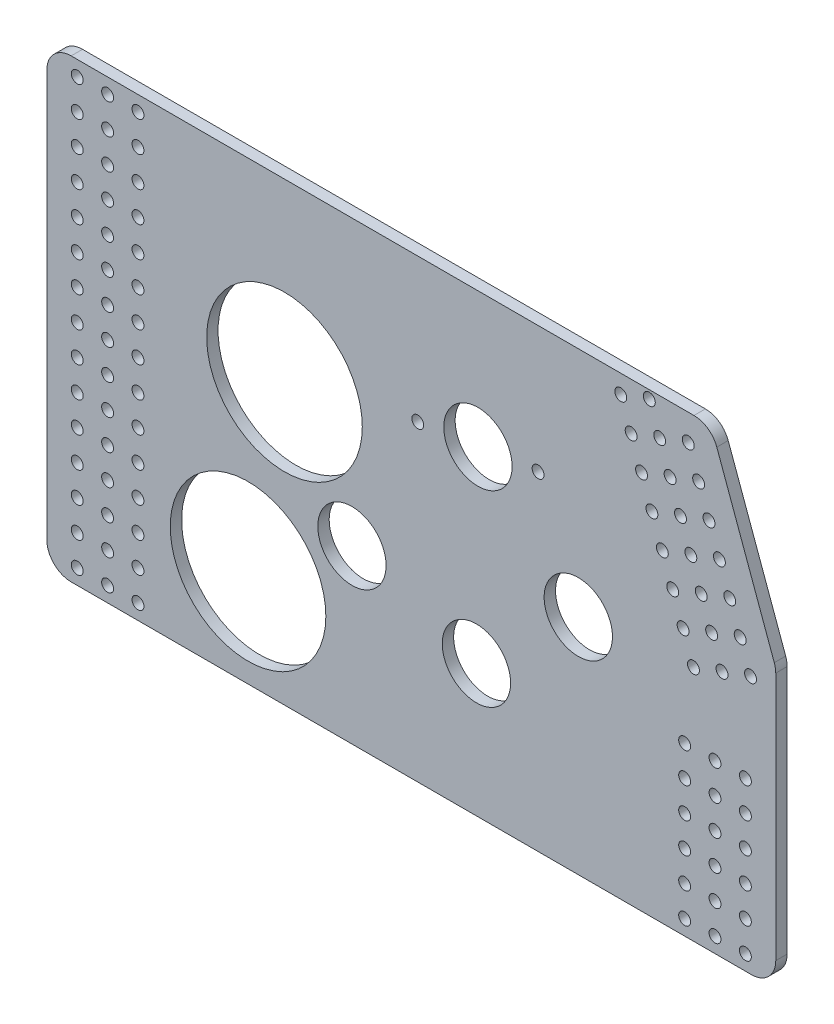
SolidWorks part; units mm, degrees
ref_plane "Front Plane" through (0, 0, 0) normal (0, 0, 1) x (1, 0, 0)
ref_plane "Top Plane" through (0, 0, 0) normal (0, 1, 0) x (1, 0, 0)
ref_plane "Right Plane" through (0, 0, 0) normal (1, 0, 0) x (0, 0, -1)
sketch "Sketch1" plane through (0, 0, 0) normal (0, 0, 1) x (1, 0, 0)
  line B0 (-152.4, 0) -> (152.4, 0)
  line B1 (152.4, 0) -> (152.4, 116.0843)
  line B2 (152.4, 116.0843) -> (125.3149, 190.5)
  line B3 (125.3149, 190.5) -> (-152.4, 190.5)
  line B4 (-152.4, 190.5) -> (-152.4, 0)
  circle B5 centre (-139.7, 184.15) radius 2.4892
  circle B6 centre (-127, 184.15) radius 2.4892
  circle B7 centre (-114.3, 184.15) radius 2.4892
  circle B8 centre (-127, 171.45) radius 2.4892
  circle B9 centre (-114.3, 171.45) radius 2.4892
  circle B10 centre (-127, 158.75) radius 2.4892
  circle B11 centre (-114.3, 158.75) radius 2.4892
  circle B12 centre (-127, 146.05) radius 2.4892
  circle B13 centre (-114.3, 146.05) radius 2.4892
  circle B14 centre (-127, 133.35) radius 2.4892
  circle B15 centre (-114.3, 133.35) radius 2.4892
  circle B16 centre (-127, 120.65) radius 2.4892
  circle B17 centre (-114.3, 120.65) radius 2.4892
  circle B18 centre (-127, 107.95) radius 2.4892
  circle B19 centre (-114.3, 107.95) radius 2.4892
  circle B20 centre (-127, 95.25) radius 2.4892
  circle B21 centre (-114.3, 95.25) radius 2.4892
  circle B22 centre (-127, 82.55) radius 2.4892
  circle B23 centre (-114.3, 82.55) radius 2.4892
  circle B24 centre (-127, 69.85) radius 2.4892
  circle B25 centre (-114.3, 69.85) radius 2.4892
  circle B26 centre (-127, 57.15) radius 2.4892
  circle B27 centre (-114.3, 57.15) radius 2.4892
  circle B28 centre (-127, 44.45) radius 2.4892
  circle B29 centre (-114.3, 44.45) radius 2.4892
  circle B30 centre (-127, 31.75) radius 2.4892
  circle B31 centre (-114.3, 31.75) radius 2.4892
  circle B32 centre (-127, 19.05) radius 2.4892
  circle B33 centre (-114.3, 19.05) radius 2.4892
  circle B34 centre (-127, 6.35) radius 2.4892
  circle B35 centre (-114.3, 6.35) radius 2.4892
  circle B36 centre (-139.7, 171.45) radius 2.4892
  circle B37 centre (-139.7, 158.75) radius 2.4892
  circle B38 centre (-139.7, 146.05) radius 2.4892
  circle B39 centre (-139.7, 133.35) radius 2.4892
  circle B40 centre (-139.7, 120.65) radius 2.4892
  circle B41 centre (-139.7, 107.95) radius 2.4892
  circle B42 centre (-139.7, 95.25) radius 2.4892
  circle B43 centre (-139.7, 82.55) radius 2.4892
  circle B44 centre (-139.7, 69.85) radius 2.4892
  circle B45 centre (-139.7, 57.15) radius 2.4892
  circle B46 centre (-139.7, 44.45) radius 2.4892
  circle B47 centre (-139.7, 31.75) radius 2.4892
  circle B48 centre (-139.7, 19.05) radius 2.4892
  circle B49 centre (-139.7, 6.35) radius 2.4892
  circle B50 centre (87.5907, 182.7494) radius 2.4892
  circle B51 centre (99.5248, 187.093) radius 2.4892
  circle B52 centre (115.8026, 179.5026) radius 2.4892
  circle B53 centre (91.9344, 170.8153) radius 2.4892
  circle B54 centre (103.8685, 175.1589) radius 2.4892
  circle B55 centre (120.1462, 167.5685) radius 2.4892
  circle B56 centre (96.278, 158.8812) radius 2.4892
  circle B57 centre (108.2121, 163.2248) radius 2.4892
  circle B58 centre (124.4899, 155.6344) radius 2.4892
  circle B59 centre (100.6217, 146.9471) radius 2.4892
  circle B60 centre (112.5558, 151.2907) radius 2.4892
  circle B61 centre (128.8335, 143.7003) radius 2.4892
  circle B62 centre (104.9653, 135.013) radius 2.4892
  circle B63 centre (116.8994, 139.3566) radius 2.4892
  circle B64 centre (133.1772, 131.7662) radius 2.4892
  circle B65 centre (109.309, 123.0789) radius 2.4892
  circle B66 centre (121.2431, 127.4226) radius 2.4892
  circle B67 centre (137.5208, 119.8321) radius 2.4892
  circle B68 centre (113.6526, 111.1448) radius 2.4892
  circle B69 centre (125.5867, 115.4885) radius 2.4892
  circle B70 centre (141.8645, 107.898) radius 2.4892
  circle B71 centre (117.9963, 99.2107) radius 2.4892
  circle B72 centre (129.9304, 103.5544) radius 2.4892
  circle B73 centre (146.2081, 95.9639) radius 2.4892
  circle B74 centre (114.3, 69.85) radius 2.4892
  circle B75 centre (127, 69.85) radius 2.4892
  circle B76 centre (139.7, 69.85) radius 2.4892
  circle B77 centre (114.3, 57.15) radius 2.4892
  circle B78 centre (127, 57.15) radius 2.4892
  circle B79 centre (139.7, 57.15) radius 2.4892
  circle B80 centre (114.3, 44.45) radius 2.4892
  circle B81 centre (127, 44.45) radius 2.4892
  circle B82 centre (139.7, 44.45) radius 2.4892
  circle B83 centre (114.3, 31.75) radius 2.4892
  circle B84 centre (127, 31.75) radius 2.4892
  circle B85 centre (139.7, 31.75) radius 2.4892
  circle B86 centre (114.3, 19.05) radius 2.4892
  circle B87 centre (127, 19.05) radius 2.4892
  circle B88 centre (139.7, 19.05) radius 2.4892
  circle B89 centre (114.3, 6.35) radius 2.4892
  circle B90 centre (127, 6.35) radius 2.4892
  circle B91 centre (139.7, 6.35) radius 2.4892
  circle B92 centre (11.8508, 132.0168) radius 14.2875
  circle B93 centre (-24.8197, 71.7449) radius 14.2875
  circle B94 centre (57.6351, 95.7125) radius 14.2875
  circle B95 centre (23.7546, 49.6787) radius 14.2875
  circle B96 centre (-65.2702, 36.9534) radius 29.9974
  circle B97 centre (-65.2702, 106.5494) radius 29.9974
  circle B98 centre (-7.8935, 147.9957) radius 2.4892
  circle B99 centre (31.595, 116.038) radius 2.4892
  circle B100 centre (5.6698, 80.2095) radius 2.4892
  circle B101 centre (41.8394, 80.2095) radius 2.4892
  circle B102 centre (41.8394, 19.1479) radius 2.4892
  circle B103 centre (5.6698, 19.1479) radius 2.4892
sketch_block_instance "Block-OuterPlate-1"
sketch_block "Block-OuterPlate" parameters "D1"=4.9784, "D7"=4.9784, "D8"=4.9784, "D9"=4.9784, "D11"=4.9784, "D12"=4.9784, "D13"=4.9784, "D15"=59.9948, "D16"=59.9948, "D17"=28.575, "D18"=28.575, "D19"=28.575, "D20"=28.575, "D21"=4.9784, "D22"=4.9784, "D23"=4.9784, "D24"=4.9784, "D25"=4.9784, "D26"=4.9784, "D2"=6.35, "D3"=12.7, "D4"=12.7, "D5"=12.7, "D6"=6.35, "D10"=12.7, "D14"=12.7, "D27"=36.1696, "D28"=18.0848, "D29"=30.5308, "D30"=30.5308
extrude "Boss-Extrude1" add sketch "Sketch1" along normal blind 4.7625
sketch "Sketch2" plane through (0, 0, 4.7625) normal (0, 0, 1) x (1, 0, 0)
  circle A0 centre (146.2081, 95.9639) radius 2.4892
  dimension "D1" = 4.9784
extrude "Boss-Extrude2" add sketch "Sketch2" against normal blind 3.175
fillet "Fillet1" radius 10.16 5 edges at (-152.4, 0, 2.3813) (152.4, 0, 2.3813) (152.4, 116.0843, 2.3813) (125.3149, 190.5, 2.3813) (-152.4, 190.5, 2.3813)
sketch "Sketch7" plane through (0, 0, 4.7625) normal (0, 0, 1) x (1, 0, 0)
  circle A0 centre (11.8508, 132.0168) radius 14.2875 construction
  circle A1 centre (57.6351, 95.7125) radius 14.2875 construction
  circle A2 centre (23.7546, 49.6787) radius 14.2875 construction
  circle A3 centre (11.8508, 132.0168) radius 14.2875
  circle A4 centre (57.6351, 95.7125) radius 14.2875
  circle A5 centre (23.7546, 49.6787) radius 14.2875
  circle A6 centre (41.8394, 19.1479) radius 2.4892 construction
  circle A7 centre (5.6698, 19.1479) radius 2.4892 construction
  circle A8 centre (-7.8935, 147.9957) radius 2.4892 construction
  circle A9 centre (31.595, 116.038) radius 2.4892 construction
  circle A10 centre (41.8394, 80.2095) radius 2.4892 construction
  circle A11 centre (5.6698, 80.2095) radius 2.4892 construction
  circle A12 centre (41.8394, 19.1479) radius 2.4892
  circle A13 centre (5.6698, 19.1479) radius 2.4892
  circle A14 centre (-7.8935, 147.9957) radius 2.4892
  circle A15 centre (31.595, 116.038) radius 2.4892
  circle A16 centre (41.8394, 80.2095) radius 2.4892
  circle A17 centre (5.6698, 80.2095) radius 2.4892
extrude "Boss-Extrude4" add sketch "Sketch7" against normal up to surface (4.7625 mm away) up to face at (25.4598, 99.6963, 0)
sketch "Sketch8" plane through (0, 0, 4.7625) normal (0, 0, 1) x (1, 0, 0)
  line L0 (2.7114, 130.4399) -> (53.017, 137.5099) construction
  line L1 (27.8642, 133.9749) -> (2.7114, 133.9749) construction
  line L2 (2.7114, 130.4399) -> (2.7114, 133.9749) construction
  circle A0 centre (-24.8197, 71.7449) radius 14.2875 construction
  circle A1 centre (-24.8197, 71.7449) radius 14.2875
  circle A2 centre (-24.8197, 71.7449) radius 13.97
  circle A3 centre (27.2348, 55.2349) radius 40.64
  circle A4 centre (27.2348, 55.2349) radius 14.2875
  circle A5 centre (27.2348, 55.2349) radius 22.86
  circle A6 centre (69.8319, 93.3349) radius 34.29
  circle A7 centre (69.8319, 93.3349) radius 14.2875
  circle A8 centre (69.8319, 93.3349) radius 12.7
  circle A9 centre (27.8642, 133.9749) radius 45.72
  circle A10 centre (27.8642, 133.9749) radius 14.2875
  circle A11 centre (53.017, 137.5099) radius 2.4892
  circle A12 centre (2.7114, 130.4399) radius 2.4892
  dimension "D1" = 27.94
  dimension "D2" = 81.28
  dimension "D3" = 28.575
  dimension "D4" = 45.72
  dimension "D5" = 68.58
  dimension "D6" = 28.575
  dimension "D7" = 25.4
  dimension "D8" = 91.44
  dimension "D12" = 28.575
  dimension "D13" = 50.8
  dimension "D14" = 4.9784
  dimension "D9" = 16.51
  dimension "D10" = 38.1
  dimension "D11" = 40.64
  dimension "D15" = 8
extrude "Cut-Extrude1" cut sketch "Sketch8" against normal through all contours A4 | A8 | A9 A7 A8 | A10 | A7 A9 | A12 | A11 region at (69.8319, 93.3349, 4.7625) region at (58.9004, 99.8547, 4.7625) region at (60.198, 102.664, 4.7625) region at (27.2348, 55.2349, 4.7625) region at (27.8642, 133.9749, 4.7625) region at (53.017, 137.5099, 4.7625) region at (2.7114, 130.4399, 4.7625)
sketch "Sketch11" plane through (0, 0, 4.7625) normal (0, 0, 1) x (1, 0, 0)
  circle A0 centre (-65.2702, 36.9534) radius 29.9974 construction
  circle A1 centre (-65.2702, 106.5494) radius 29.9974 construction
  circle A2 centre (-65.2702, 36.9534) radius 29.9974
  circle A3 centre (-65.2702, 106.5494) radius 29.9974
extrude "Boss-Extrude5" add sketch "Sketch11" against normal up to surface (4.7625 mm away) up to face at (41.5223, 55.2349, 0)
sketch "Sketch10" plane through (0, 0, 4.7625) normal (0, 0, 1) x (1, 0, 0)
  circle A0 centre (-24.8197, 71.7449) radius 14.2875 construction
  circle A1 centre (-24.8197, 71.7449) radius 14.2875
  circle A2 centre (-24.8197, 71.7449) radius 45.72
  circle A3 centre (-53.0343, 117.0118) radius 7.62
  circle A5 centre (-68.2743, 40.8118) radius 7.62
  circle A6 centre (-53.0343, 117.0118) radius 32.5374
  circle A8 centre (-68.2743, 40.8118) radius 32.5374
  dimension "D1" = 91.44
  dimension "D2" = 15.24
  dimension "D5" = 65.0748
  dimension "D6" = 65.0748
  dimension "D3" = 76.2
  dimension "D4" = 15.24
extrude "Cut-Extrude2" cut sketch "Sketch10" against normal through all contours A2 A8 A5 | A2 A8 | A2 A6 A3 | A2 A6 | A3 | A5 region at (-42.6521, 100.3548, 4.7625) region at (-53.0343, 117.0118, 4.7625) region at (-57.6271, 124.3804, 4.7625) region at (-68.2743, 40.8118, 4.7625) region at (-75.3479, 35.7764, 4.7625) region at (-52.2842, 52.1943, 4.7625)
